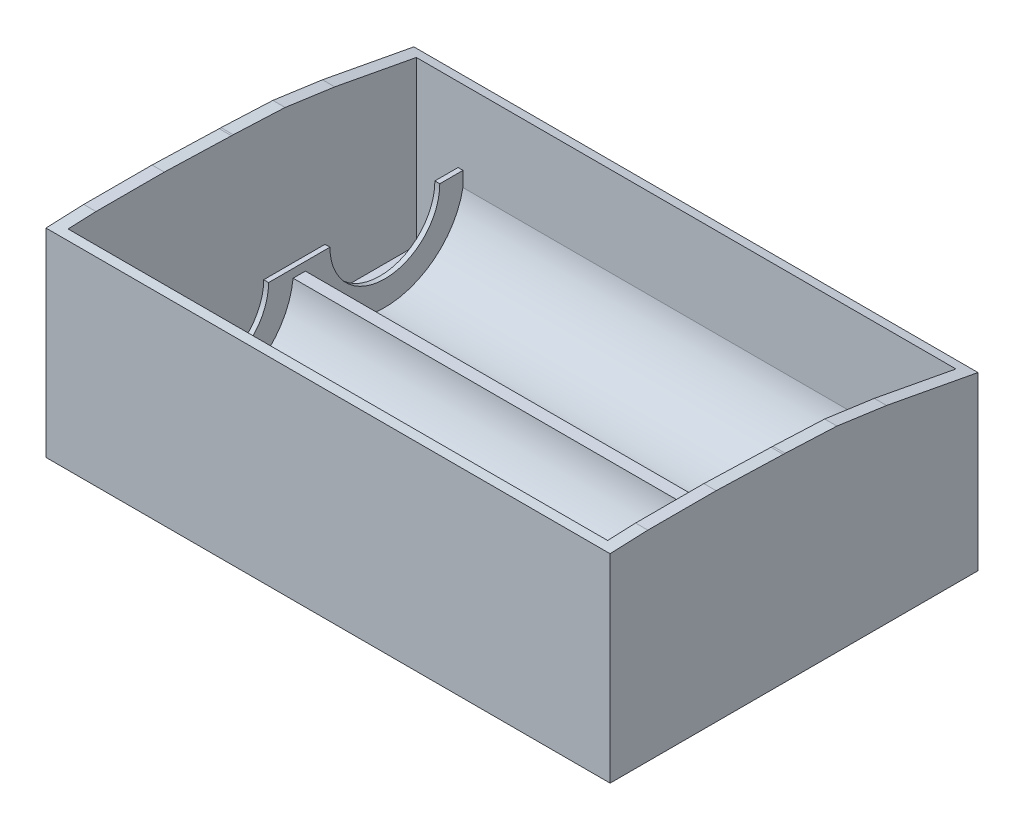
SolidWorks part; units mm, degrees
ref_plane "Front Plane" through (0, 0, 0) normal (0, 0, 1) x (1, 0, 0)
ref_plane "Top Plane" through (0, 0, 0) normal (0, 1, 0) x (1, 0, 0)
ref_plane "Right Plane" through (0, 0, 0) normal (1, 0, 0) x (0, 0, -1)
sketch "Sketch16" plane through (0, 0, 0) normal (1, 0, 0) x (0, 0, -1)
  line L0 (21.5465, 40.6394) -> (7.6186, 40.6394)
  line L1 (21.5465, 40.6394) -> (35.2383, 40.2055)
  line L2 (35.2383, 40.2055) -> (35.6026, 40.2055)
  line L3 (35.6026, 40.2055) -> (46.1712, 39.7312)
  line L4 (46.1712, 39.7312) -> (56.2876, 38.3122)
  line L5 (56.2876, 38.3122) -> (74.9264, 34.8087)
  line L6 (74.9264, 34.8087) -> (74.9264, -0.1913)
  line L7 (-0.0736, -0.1913) -> (74.9264, -0.1913)
  line L8 (-0.0736, -0.1913) -> (-0.0736, 40.3184)
  line L9 (-0.0736, 40.3184) -> (7.6186, 40.6394)
  dimension "D1" = 75
  dimension "D2" = 35
extrude "Boss-Extrude6" add sketch "Sketch16" along normal blind 115
sketch "Sketch17" plane through (0, 0, 0) normal (0, 1, 0) x (1, 0, 0)
  line L0 (0, 74.9264) -> (0, 56.2876) construction
  line L1 (2.5, 72.9264) -> (112.5, 72.9264)
  line L2 (2.5, 72.9264) -> (2.5, 1.9264)
  line L3 (2.5, 1.9264) -> (112.5, 1.9264)
  line L4 (112.5, 72.9264) -> (112.5, 1.9264)
  line L8 (115, 74.9264) -> (0, 74.9264) construction
  dimension "D1" = 110
  dimension "D2" = 2.5
  dimension "D3" = 71
  dimension "D4" = 2
extrude "Cut-Extrude5" cut sketch "Sketch17" along normal blind 115 from offset 2
sketch "Sketch18" plane through (0, 2, 0) normal (0, 1, 0) x (1, 0, 0)
  line L0 (0, 56.2876) -> (0, 46.1712) construction
  line L1 (12, 71.4264) -> (103, 71.4264)
  line L2 (12, 71.4264) -> (12, 3.4264)
  line L3 (12, 3.4264) -> (103, 3.4264)
  line L4 (103, 71.4264) -> (103, 3.4264)
  line L5 (112.5, 72.9264) -> (2.5, 72.9264) construction
  dimension "D1" = 91
  dimension "D2" = 12
  dimension "D3" = 68
  dimension "D4" = 1.5
sketch "Sketch21" plane through (0, 0, 0) normal (-1, 0, 0) x (0, 0, 1)
  line L0 (-73.213, 2) -> (-73.213, 20)
  line L1 (-5.8972, 2) -> (-5.8972, 20)
  line L2 (-40.8051, 18.2725) -> (-38.3051, 18.2725)
  line L3 (-71.4264, 2) -> (-3.4264, 2) construction
  line L4 (-73.213, 2) -> (-5.8972, 2)
  arc A0 (-73.213, 20) -> (-40.8051, 18.2725) centre (-56.963, 20) ccw
  arc A1 (-5.8972, 20) -> (-38.3051, 18.2725) centre (-22.1472, 20) cw
  point P11 (-73.1913, 2)
  dimension "D2" = 16.25
  dimension "D3" = 16.25
  dimension "D4" = 18
  dimension "D1" = 2.5
  dimension "D5" = 18
extrude "Boss-Extrude7" add sketch "Sketch21" against normal up to vertex (103 mm away) from vertex up to point (103, 2, -71.4264) starting at point (12, 2, -71.4264)
sketch "Sketch22" plane through (0, 2, 0) normal (0, 1, 0) x (1, 0, 0)
  line L0 (12, 5.8972) -> (12, 1.9264)
  line L1 (2.5, 1.9264) -> (112.5, 1.9264) construction
  line L2 (12, 1.9264) -> (103, 1.9264)
  line L3 (2.5, 1.9264) -> (112.5, 1.9264) construction
  line L4 (103, 1.9264) -> (103, 5.8972)
  line L5 (103, 5.8972) -> (12, 5.8972)
  line L7 (12, 72.9264) -> (2.5, 72.9264) construction
  line L8 (2.5, 72.9264) -> (2.5, 1.9264) construction
  line L9 (112.5, 1.9264) -> (112.5, 7.6186) construction
  circle A0 centre (7, 69.4264) radius 3
  circle A1 centre (108, 69.4264) radius 3
  circle A2 centre (108, 5.4264) radius 3
  circle A3 centre (7, 5.4264) radius 3
  dimension "D5" = 6
  dimension "D1" = 3.5
  dimension "D2" = 3.5
  dimension "D3" = 4.5
  dimension "D4" = 4.5
extrude "Cut-Extrude6" cut sketch "Sketch22" against normal through all
sketch "Sketch23" plane through (0, 0, 0) normal (-1, 0, 0) x (0, 0, 1)
  line L0 (-73.213, 20) -> (-5.8972, 20)
  line L1 (-5.8972, 20) -> (-5.8972, 2)
  line L2 (-5.8972, 2) -> (-73.213, 2)
  line L3 (-73.213, 2) -> (-73.213, 20)
extrude "Boss-Extrude8" add sketch "Sketch23" along normal blind 1 from surface starting at face at (12, 8.0483, -39.2288)
sketch "Sketch24" plane through (115, 0, 0) normal (1, 0, 0) x (0, 0, -1)
  line L0 (5.8972, 20) -> (73.213, 20)
  line L1 (73.213, 20) -> (73.213, 2)
  line L2 (73.213, 2) -> (5.8972, 2)
  line L3 (5.8972, 2) -> (5.8972, 20)
extrude "Boss-Extrude9" add sketch "Sketch24" along normal blind 1 from surface starting at face at (103, 8.0483, -39.2288)
sketch "Sketch25" plane through (11, 0, 0) normal (-1, 0, 0) x (0, 0, 1)
  line L6 (-68.2051, 20) -> (-45.8051, 20)
  line L7 (-33.3051, 20) -> (-10.9051, 20)
  arc A0 (-68.2051, 20) -> (-45.8051, 20) centre (-57.0051, 20) ccw
  arc A1 (-33.3051, 20) -> (-10.9051, 20) centre (-22.1051, 20) ccw
  dimension "D1" = 11.2
  dimension "D2" = 11.2
  dimension "D3" = 5
  dimension "D4" = 5
extrude "Cut-Extrude7" cut sketch "Sketch25" against normal up to surface (1 mm away) up to face at (12, 12.858, -45.8952)
sketch "Sketch26" plane through (104, 0, 0) normal (1, 0, 0) x (0, 0, -1)
  line L10 (10.9051, 20) -> (33.3051, 20)
  line L11 (45.8051, 20) -> (68.2051, 20)
  arc A2 (10.9051, 20) -> (33.3051, 20) centre (22.1051, 20) ccw
  arc A3 (45.8051, 20) -> (68.2051, 20) centre (57.0051, 20) ccw
  dimension "D1" = 11.2
  dimension "D4" = 11.2
extrude "Cut-Extrude8" cut sketch "Sketch26" against normal up to surface (1 mm away) up to face at (103, 12.858, -45.8952)
